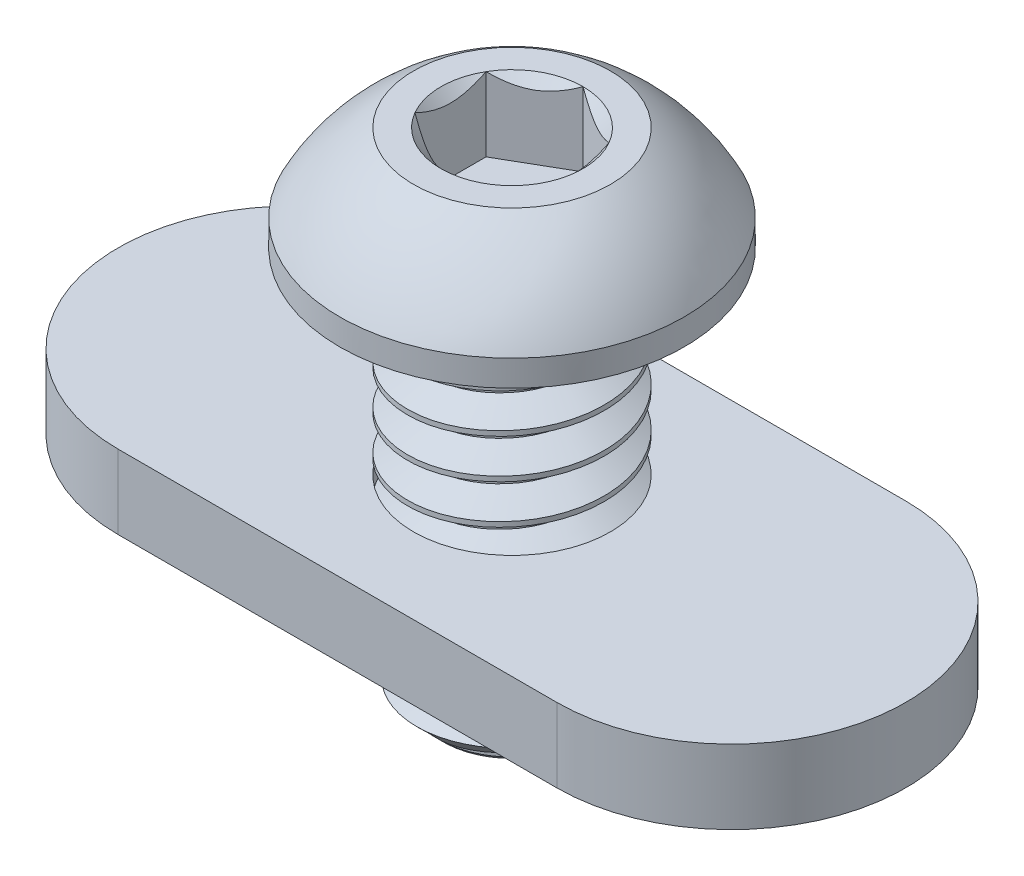
SolidWorks part; units mm, degrees
ref_plane "Front Plane" through (0, 0, 0) normal (0, 0, 1) x (1, 0, 0)
ref_plane "Top Plane" through (0, 0, 0) normal (0, 1, 0) x (1, 0, 0)
ref_plane "Right Plane" through (0, 0, 0) normal (1, 0, 0) x (0, 0, -1)
sketch "Sketch1" plane through (0, 0, 0) normal (0, 1, 0) x (1, 0, 0)
  circle A0 centre (0, 0) radius 3.175
  point P3 (-3.175, 0)
  point P4 (3.175, 0)
  dimension "D1" = 6.35
extrude "Boss-Extrude1" add sketch "Sketch1" against normal blind 12.7
sketch "Sketch2" plane through (0, -12.7, 0) normal (0, -1, 0) x (1, 0, 0)
  circle A1 centre (0, 0) radius 3.175
  circle A2 centre (0, 0) radius 3.175
  point P0 (0, -3.175)
  dimension "D1" = 0
curve "Helix/Spiral1" pitch 1.27 height 13.97 turns 11
sketch "Sketch3" plane through (0, 0, 0) normal (1, 0, 0) x (0, 0, -1)
  line L0 (3.3125, -12.6206) -> (2.2126, -13.2556) construction
  line L1 (2.2126, -13.2556) -> (3.3125, -13.8906) construction
  line L2 (3.3125, -13.8906) -> (3.3125, -12.6206) construction
  line L3 (2.3501, -13.1762) -> (2.3501, -13.335) construction
  line L4 (3.175, -12.7) -> (3.175, -13.8112) construction
  line L5 (2.2126, -13.2556) -> (2.3501, -13.2556) construction
  line L6 (3.175, -13.2556) -> (3.3125, -13.2556) construction
  line L8 (2.2126, -13.2556) -> (-3.175, -13.2556) construction
  line L9 (2.3501, -13.1762) -> (3.2437, -12.6603)
  line L10 (2.3501, -13.1762) -> (2.3501, -13.335)
  line L11 (2.3501, -13.335) -> (3.2437, -13.8509)
  line L12 (3.2437, -13.8509) -> (3.2437, -12.6603)
  line L14 (-3.175, -13.2556) -> (-3.175, -11.9856) construction
  line L15 (-3.175, -11.9856) -> (-3.175, -10.7156) construction
  line L16 (-3.175, -10.7156) -> (-3.175, -9.4456) construction
  line L17 (-3.175, -9.4456) -> (-3.175, -8.1756) construction
  line L18 (-3.175, 0) -> (-3.175, -12.7) construction
  point P15 (3.2437, -13.2556)
  dimension "D1" = 1.27
  dimension "D2" = 0.1588
sweep "Cut-Sweep1" cut profiles "Sketch3" path "Helix/Spiral1" align with end faces yes
sketch "Sketch4" plane through (0, -12.7, 0) normal (0, -1, 0) x (1, 0, 0)
  circle A0 centre (0, 0) radius 2.2126
extrude "Cut-Extrude1" cut sketch "Sketch4" against normal blind 1.27 draft 45 flip side to cut
sketch "Sketch5" plane through (0, 0, 0) normal (0, 0, 1) x (1, 0, 0)
  line L0 (0, 0) -> (0, 3.3528)
  line L1 (-5.5499, 0) -> (0, 0)
  line L2 (0, 3.3528) -> (-3.175, 3.3528)
  line L4 (-5.5499, 0.8382) -> (-5.5499, 0)
  line L5 (0, 0) -> (0, -12.7) construction
  arc A0 (-3.175, 3.3528) -> (-5.5499, 0.8382) centre (0, -2.0246) ccw
  dimension "D1" = 3.3528
  dimension "D2" = 0.8382
  dimension "D4" = 11.0998
revolve "Revolve1" add sketch "Sketch5" angle 360 mid plane about L0
sketch "Sketch6" plane through (0, 3.3528, 0) normal (0, 1, 0) x (1, 0, 0)
  line L1 (0, 2.2914) -> (-1.9844, 1.1457)
  line L2 (-1.9844, 1.1457) -> (-1.9844, -1.1457)
  line L3 (-1.9844, -1.1457) -> (0, -2.2914)
  line L4 (0, -2.2914) -> (1.9844, -1.1457)
  line L5 (1.9844, -1.1457) -> (1.9844, 1.1457)
  line L6 (1.9844, 1.1457) -> (0, 2.2914)
  circle A0 centre (0, 0) radius 1.9844 construction
  dimension "D1" = 3.9688
extrude "Cut-Extrude2" cut sketch "Sketch6" against normal blind 2.3813
sketch "Sketch7" plane through (0, 3.3528, 0) normal (0, 1, 0) x (1, 0, 0)
  circle A0 centre (0, 0) radius 2.2914
extrude "Cut-Extrude3" cut sketch "Sketch7" against normal blind 2.3813 draft 45
sketch "Sketch8" plane through (0, 0, 0) normal (0, 1, 0) x (1, 0, 0)
  line L0 (-7.0739, 0) -> (7.0739, 0) construction
  line L1 (-7.0739, 5.6261) -> (7.0739, 5.6261)
  line L2 (-7.0739, -5.6261) -> (7.0739, -5.6261)
  line L4 (-12.7, 5.6261) -> (12.7, 5.6261) construction
  line L5 (-12.7, 5.6261) -> (-12.7, -5.6261) construction
  line L6 (-12.7, -5.6261) -> (12.7, -5.6261) construction
  line L7 (12.7, 5.6261) -> (12.7, -5.6261) construction
  arc A0 (-7.0739, 5.6261) -> (-7.0739, -5.6261) centre (-7.0739, 0) ccw
  arc A1 (7.0739, -5.6261) -> (7.0739, 5.6261) centre (7.0739, 0) ccw
  circle A3 centre (0, 0) radius 3.175
  circle A4 centre (0, 0) radius 3.175
  point P2 (0, 0)
  dimension "D2" = 25.4
  dimension "D3" = 11.2522
  dimension "D1" = 0
extrude "Boss-Extrude2" add sketch "Sketch8" against normal blind 2.3876 from offset 6.35 separate body offset against normal yes
sketch "Sketch9" plane through (0, -8.7376, 0) normal (0, -1, 0) x (1, 0, 0)
  circle A1 centre (0, 0) radius 3.175 construction
  circle A2 centre (0, 0) radius 3.175
  circle A3 centre (0, 0) radius 3.5687
  dimension "D1" = 7.1374
extrude "Boss-Extrude3" add sketch "Sketch9" along normal blind 0.762
sketch "SketchZ" plane through (0, 0, 0) normal (0, 0, 1) x (1, 0, 0)
  line L0 (3.175, -12.9381) -> (3.175, -11.6681) construction
  line L2 (0, -13.2556) -> (0, -11.9856) construction
  line L4 (3.175, -12.9381) -> (0, -12.9381) construction
  line L5 (0, -9.4456) -> (0, -8.1756) construction
  line L6 (0, -12.6206) -> (0, -13.2556) construction
equation "\"D3@Helix/Spiral1\" = \"D4@Helix/Spiral1\" + \"D1@Boss-Extrude1\""
equation "\"D1@Sketch3\" = \"D4@Helix/Spiral1\""
equation "\"D2@Sketch3\" = \"D1@Sketch3\" / 8"
equation "\"D1@Cut-Extrude1\" = \"D4@Helix/Spiral1\""
equation "\"D1@Cut-Extrude2\" = \"D1@Sketch6\" * 3/5"
equation "\"D1@Cut-Extrude3\" = \"D1@Cut-Extrude2\""
equation "\"D2@Sketch5\" = \"D1@Sketch5\" * 1/4"
